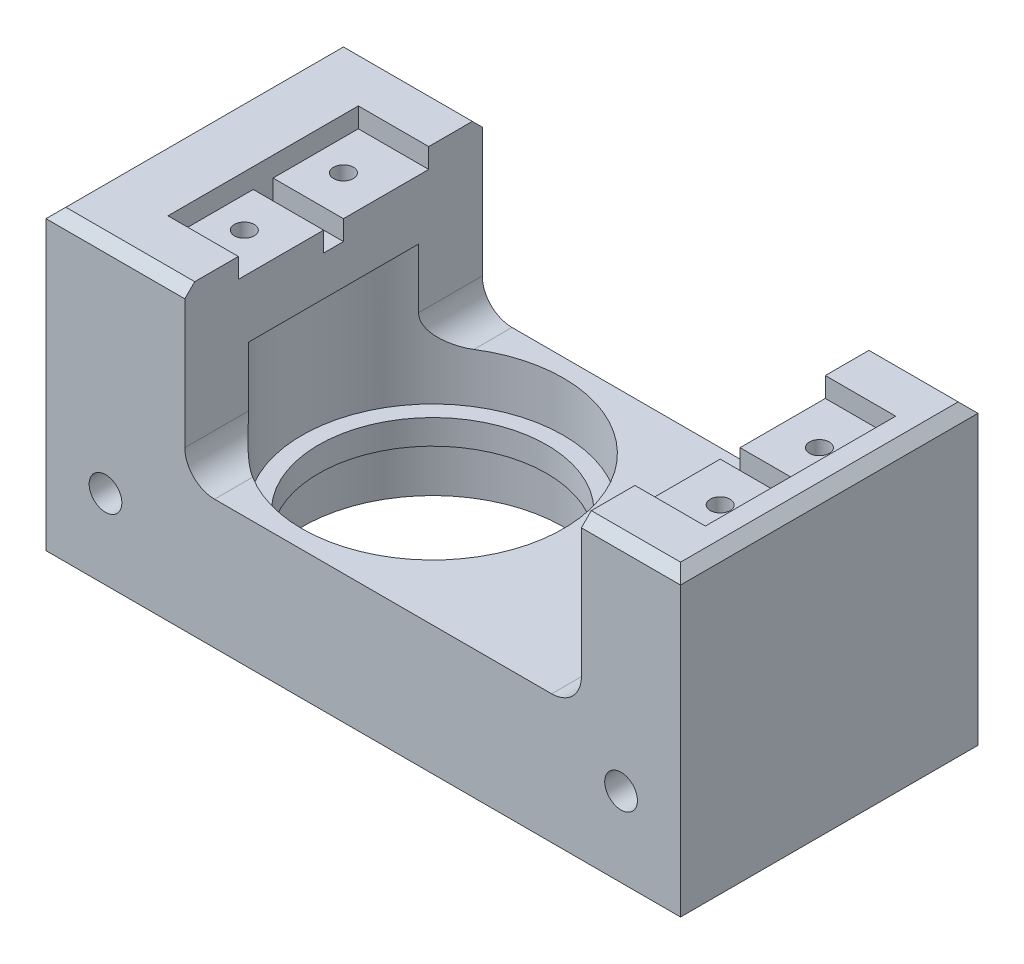
SolidWorks part; units mm, degrees
ref_plane "Спереди" through (0, 0, 0) normal (0, 0, 1) x (1, 0, 0)
ref_plane "Сверху" through (0, 0, 0) normal (0, 1, 0) x (1, 0, 0)
ref_plane "Справа" through (0, 0, 0) normal (1, 0, 0) x (0, 0, -1)
sketch "Эскиз1" plane through (0, 0, 0) normal (0, 1, 0) x (1, 0, 0)
  line L0 (0, 15) -> (0, -15) construction
  line L1 (-24, 15) -> (40, 15)
  line L2 (-24, 15) -> (-24, -15)
  line L3 (-24, -15) -> (40, -15)
  line L4 (40, 15) -> (40, -15)
  line L6 (-24, 0) -> (40, 0) construction
  point P6 (0, 0)
  dimension "D1" = 30
  dimension "D2" = 24
  dimension "D3" = 40
extrude "тело для подшипников" add sketch "Эскиз1" along normal blind 13
sketch "Эскиз2" plane through (0, 13, 0) normal (0, 1, 0) x (1, 0, 0)
  circle A0 centre (0, 0) radius 13.175
  dimension "D1" = 26.35
extrude "подшипник верхний" cut sketch "Эскиз2" against normal blind 5
sketch "Эскиз3" plane through (0, 0, 0) normal (0, -1, 0) x (1, 0, 0)
  circle A0 centre (0, 0) radius 13.175
  dimension "D1" = 26.35
extrude "подшипник нижний" cut sketch "Эскиз3" against normal blind 5.5
sketch "Эскиз4" plane through (0, 8, 0) normal (0, 1, 0) x (1, 0, 0)
  circle A0 centre (0, 0) radius 11.5
  dimension "D1" = 23
extrude "отверстие под ось" cut sketch "Эскиз4" against normal through all
sketch "Эскиз8" plane through (0, 13, 0) normal (0, 1, 0) x (1, 0, 0)
  line L0 (-24, 0) -> (40, 0) construction
  line L1 (-24, 15) -> (40, 15)
  line L2 (-24, 15) -> (-24, -15)
  line L3 (-24, -15) -> (40, -15)
  line L4 (40, 15) -> (40, -15)
  line L5 (-24, 15) -> (-24, -15) construction
  line L6 (0, 15) -> (0, -15) construction
  circle A0 centre (0, 0) radius 13.175
  circle A1 centre (0, 0) radius 13.175 construction
  dimension "D2" = 40
extrude "основание под сервой" add sketch "Эскиз8" along normal blind 3
sketch "Эскиз9" plane through (0, 16, 0) normal (0, 1, 0) x (1, 0, 0)
  line L0 (40, 15) -> (-24, 15) construction
  line L1 (-20, 15) -> (-10, 15)
  line L2 (-20, 15) -> (-20, -15)
  line L3 (-20, -15) -> (-10, -15)
  line L4 (-10, 15) -> (-10, 8.5779)
  line L5 (-24, -15) -> (40, -15) construction
  line L6 (0, 15) -> (0, -15) construction
  line L7 (40, 15) -> (30, 15)
  line L8 (40, 15) -> (40, -15)
  line L9 (40, -15) -> (30, -15)
  line L10 (30, 15) -> (30, -15)
  line L11 (-10, -8.5779) -> (-10, -15)
  line L12 (-24, 15) -> (-24, -15) construction
  arc A0 (-10, 8.5779) -> (-10, -8.5779) centre (0, 0) ccw
  circle A1 centre (0, 0) radius 13.175 construction
  dimension "D1" = 20
  dimension "D2" = 40
  dimension "D3" = 10
  dimension "D4" = 10
extrude "выступы к серве" add sketch "Эскиз9" along normal blind 12
sketch "Эскиз10" plane through (0, 28, 0) normal (0, 1, 0) x (1, 0, 0)
  line L0 (-20, 0) -> (40, 0) construction
  line L1 (-20, 15) -> (-20, -15) construction
  line L2 (40, -15) -> (40, 15) construction
  line L3 (-14, 5) -> (-14, -5) construction
  line L5 (34, 5) -> (34, -5) construction
  circle A0 centre (-14, 5) radius 1
  circle A1 centre (-14, -5) radius 1
  circle A2 centre (34, -5) radius 1
  circle A3 centre (34, 5) radius 1
  point P14 (34, 0)
  point P15 (-14, 0)
  dimension "D1" = 2
  dimension "D2" = 10
  dimension "D3" = 14
  dimension "D4" = 34
extrude "крепление сервы" cut sketch "Эскиз10" against normal blind 12
sketch "Эскиз11" plane through (0, 0, 15) normal (0, 0, 1) x (1, 0, 0)
  line L0 (-24, 8) -> (40, 8) construction
  line L1 (-24, 16) -> (-24, 0) construction
  line L2 (40, 28) -> (40, 0) construction
  line L4 (0, 16) -> (0, 0) construction
  line L5 (8, 0) -> (8, 16) construction
  line L6 (-10, 16) -> (30, 16) construction
  line L8 (-24, 0) -> (40, 0) construction
  circle A0 centre (-18, 8) radius 1.65
  circle A3 centre (34, 8) radius 1.65
  dimension "D1" = 3.3
  dimension "D2" = 52
extrude "отверстия под болты" cut sketch "Эскиз11" against normal through all
sketch "Эскиз12" plane through (0, 28, 0) normal (0, 1, 0) x (1, 0, 0)
  line L0 (-10, -15) -> (-10, -8.5779) construction
  line L1 (-10, 8.5779) -> (-10, 15) construction
  line L2 (-20, 15) -> (-10, 15)
  line L3 (-20, 15) -> (-20, 9.6)
  line L4 (-20, 9.6) -> (-10, 9.6)
  line L5 (-20, -15) -> (-10, -15)
  line L6 (-10, 15) -> (-10, 9.6)
  line L7 (-20, -15) -> (-20, -9.6)
  line L8 (-20, -9.6) -> (-10, -9.6)
  line L9 (-10, -15) -> (-10, -9.6)
  line L10 (30, 15) -> (30, -15) construction
  line L11 (40, -15) -> (30, -15)
  line L12 (40, -15) -> (40, -9.6)
  line L13 (40, -9.6) -> (30, -9.6)
  line L14 (30, -15) -> (30, -9.6)
  line L15 (40, 15) -> (30, 15) construction
  line L16 (40, 15) -> (30, 15)
  line L17 (40, 15) -> (40, 9.6)
  line L18 (40, 9.6) -> (30, 9.6)
  line L19 (30, 15) -> (30, 9.6)
  line L20 (40, -15) -> (40, 15) construction
  dimension "D1" = 5.4
extrude "бортики к серве" add sketch "Эскиз12" along normal blind 2
sketch "Эскиз14" plane through (0, 16, 0) normal (0, 1, 0) x (1, 0, 0)
  line L0 (-10, 15) -> (-10, 8.5779)
  line L1 (-10, 15) -> (30, 15)
  line L2 (30, 15) -> (30, -15)
  line L3 (30, -15) -> (-10, -15)
  line L4 (-10, -15) -> (-10, -8.5779)
  arc A0 (-10, -8.5779) -> (-10, 8.5779) centre (0, 0) ccw
  arc A1 (-10, -8.5779) -> (-10, 8.5779) centre (0, 0) ccw construction
extrude "углубление впресовать подшипник" cut sketch "Эскиз14" against normal blind 3
sketch "Эскиз15" plane through (0, 28, 0) normal (0, 1, 0) x (1, 0, 0)
  line L1 (-20, 9.6) -> (-10, 9.6)
  line L2 (-20, 9.6) -> (-20, -9.6)
  line L3 (-20, -9.6) -> (-10, -9.6)
  line L4 (-10, 9.6) -> (-10, -9.6)
  circle A0 centre (-14, 5) radius 1
  circle A1 centre (-14, -5) radius 1
  circle A2 centre (-14, 5) radius 1 construction
  circle A3 centre (-14, -5) radius 1 construction
extrude "наплыв для саморезов" add sketch "Эскиз15" against normal blind 9
chamfer "Фаска5" distance 3 angle 45 1 edges at (-10, 19, 0)
sketch "Эскиз17" plane through (0, 28, 0) normal (0, 1, 0) x (1, 0, 0)
  line L0 (-10, -9.6) -> (-20, -9.6) construction
  line L1 (-20, 9.6) -> (-17.1, 9.6)
  line L2 (-20, 9.6) -> (-20, -9.6)
  line L3 (-20, -9.6) -> (-17.1, -9.6)
  line L4 (-17.1, 9.6) -> (-17.1, -9.6)
  line L5 (40, -9.6) -> (30, -9.6) construction
  line L6 (40, 9.6) -> (37.1, 9.6)
  line L7 (40, 9.6) -> (40, -9.6)
  line L8 (40, -9.6) -> (37.1, -9.6)
  line L9 (37.1, 9.6) -> (37.1, -9.6)
  line L10 (-20, 9.6) -> (-10, 9.6) construction
  line L11 (-20, 15) -> (-20, -15) construction
  line L12 (-20, 9.6) -> (-20, -9.6) construction
  dimension "D1" = 2.9
  dimension "D2" = 2.9
extrude "бортики к серве спереди" add sketch "Эскиз17" along normal up to surface (2 mm away) up to face at (-15, 30, -12.3)
sketch "Эскиз16" plane through (0, 28, 0) normal (0, 1, 0) x (1, 0, 0)
  line L0 (-17.1, 0) -> (37.1, 0) construction
  line L3 (-10, -9.6) -> (-10, 9.6) construction
  line L4 (-10, 1) -> (-17.1, 1)
  line L5 (-10, 1) -> (-10, -1)
  line L6 (-10, -1) -> (-17.1, -1)
  line L7 (-17.1, 1) -> (-17.1, -1)
  line L8 (30, 9.6) -> (30, -9.6) construction
  line L9 (30, -1) -> (37.1, -1)
  line L10 (30, -1) -> (30, 1)
  line L11 (30, 1) -> (37.1, 1)
  line L12 (37.1, -1) -> (37.1, 1)
  line L13 (-17.1, -9.6) -> (-17.1, 9.6) construction
  line L14 (-17.1, -9.6) -> (-17.1, 9.6) construction
  line L15 (37.1, 9.6) -> (37.1, -9.6) construction
  point P12 (-10, 0)
  point P19 (30, 0)
  dimension "D1" = 2
extrude "пазы под ребра жесткости сервы" cut sketch "Эскиз16" against normal blind 2
sketch "Эскиз18" plane through (0, 16, 0) normal (0, 1, 0) x (1, 0, 0)
  line L0 (-20, -15) -> (-10, -15) construction
  line L1 (-24, 15) -> (-20, 15)
  line L2 (-24, 15) -> (-24, -15)
  line L3 (-24, -15) -> (-20, -15)
  line L4 (-20, 15) -> (-20, -15)
  line L5 (-20, 15) -> (-20, -15) construction
extrude "площадка под светодиод" add sketch "Эскиз18" along normal up to surface (14 mm away) up to face at (-14.275, 30, 0)
fillet "Скругление4" radius 3 3 edges at (30, 13, 0) (-10, 13, -11.789) (-10, 13, 11.789)
chamfer "Фаска7" distance 1 angle 45 6 edges at (40, 30, 0) (-24, 30, 0) (35, 30, -15) (35, 30, 15) (-17, 30, -15) (-17, 30, 15)
